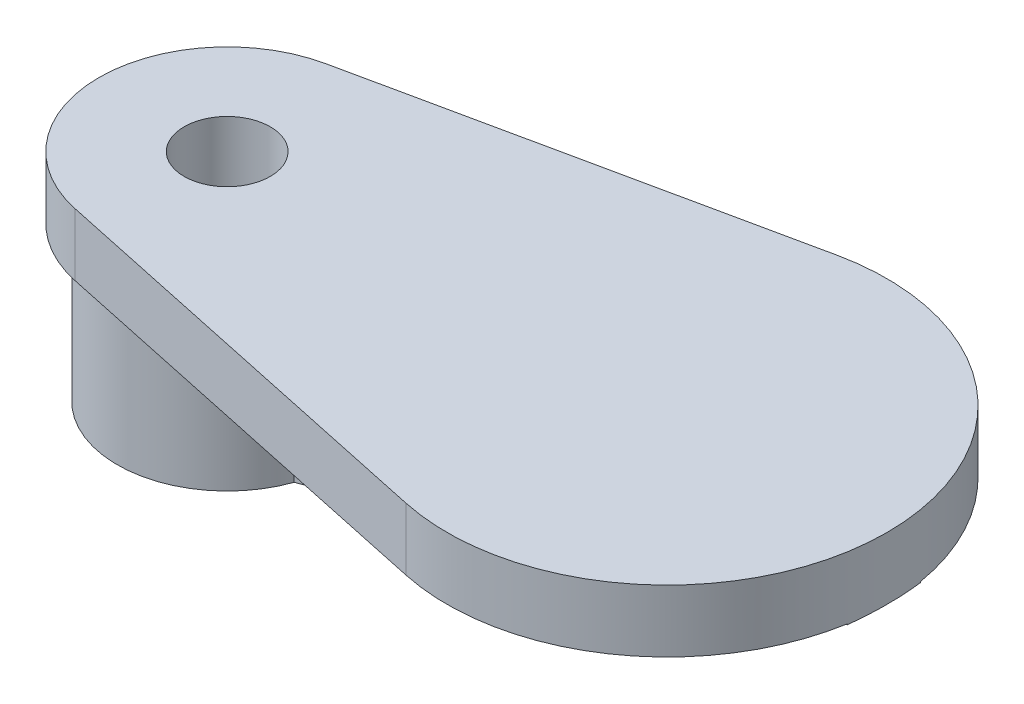
SolidWorks part; units mm, degrees
ref_plane "Front Plane" through (0, 0, 0) normal (0, 0, 1) x (1, 0, 0)
ref_plane "Top Plane" through (0, 0, 0) normal (0, 1, 0) x (1, 0, 0)
ref_plane "Right Plane" through (0, 0, 0) normal (1, 0, 0) x (0, 0, -1)
sketch "Sketch1" plane through (0, 0, 0) normal (0, 1, 0) x (1, 0, 0)
  circle A0 centre (0, 0) radius 1.175
  circle A1 centre (0, 0) radius 3
  dimension "D1" = 2.35
  dimension "D2" = 6
extrude "Boss-Extrude1" add sketch "Sketch1" along normal blind 5.9
sketch "Sketch3" plane through (0, 5.9, 0) normal (0, 1, 0) x (1, 0, 0)
  line L0 (-0.7292, 3.4232) -> (10.75, 5.8683)
  line L1 (-0.7292, -3.4232) -> (10.75, -5.8683)
  arc A0 (-0.7292, 3.4232) -> (-0.7292, -3.4232) centre (0, 0) ccw
  arc A1 (10.75, -5.8683) -> (10.75, 5.8683) centre (12, 0) ccw
  circle A2 centre (0, 0) radius 1.175 construction
  circle A3 centre (0, 0) radius 1.175
  dimension "D1" = 7
  dimension "D2" = 12
  dimension "D3" = 12
extrude "Boss-Extrude2" add sketch "Sketch3" against normal blind 1.7
sketch "Sketch4" plane through (0, 4.2, 0) normal (0, -1, 0) x (1, 0, 0)
  line L0 (0, 0) -> (18, 0) construction
  line L1 (2.8284, 1) -> (17.9161, 1)
  line L2 (2.8284, -1) -> (17.9161, -1)
  arc A0 (10.75, -5.8683) -> (10.75, 5.8683) centre (12, 0) ccw construction
  circle A1 centre (0, 0) radius 3 construction
  arc A2 (17.9161, -1) -> (17.9161, 1) centre (12, 0) ccw
  arc A3 (2.8284, -1) -> (2.8284, 1) centre (0, 0) ccw
  dimension "D1" = 1
extrude "Boss-Extrude3" add sketch "Sketch4" along normal up to surface (4.2 mm away) up to face at (0, 0, 3)
sketch "Sketch5" plane through (0, 0, 0) normal (0, 0, 1) x (1, 0, 0)
  line L0 (2.8284, 0) -> (18, 4.2)
  line L1 (18, 0) -> (18, 5.9) construction
  line L2 (2.8284, 0) -> (18, 0)
  line L3 (18, 0) -> (18, 4.2)
extrude "Cut-Extrude1" cut sketch "Sketch5" against normal through all both and the other way through all
chamfer "Chamfer2" distance 0.5 angle 45 1 edges at (-3, 4.2, 0)
